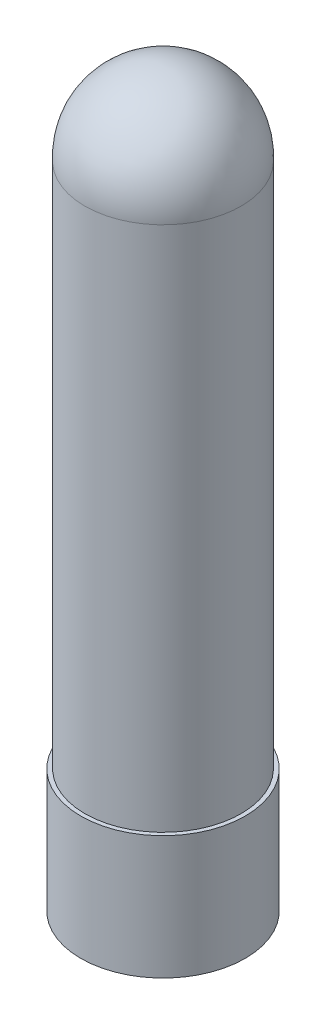
SolidWorks part; units mm, degrees
ref_plane "Front Plane" through (0, 0, 0) normal (0, 0, 1) x (1, 0, 0)
ref_plane "Top Plane" through (0, 0, 0) normal (0, 1, 0) x (1, 0, 0)
ref_plane "Right Plane" through (0, 0, 0) normal (1, 0, 0) x (0, 0, -1)
sketch "Sketch1" plane through (0, 0, 0) normal (0, 1, 0) x (1, 0, 0)
  circle A0 centre (0, 0) radius 10
extrude "Boss-Extrude1" add sketch "Sketch1" along normal blind 15
sketch "Sketch3" plane through (0, 0, 0) normal (0, -1, 0) x (1, 0, 0)
  circle A0 centre (0, 0) radius 9.5
extrude "Boss-Extrude3" add sketch "Sketch3" against normal blind 64 from surface starting at face at (0, 15, 10)
sketch "Sketch2" plane through (0, 0, 0) normal (0, 0, 1) x (1, 0, 0)
  line L0 (0, 75.9639) -> (-2.5, 62.1786)
  line L1 (-2.5, 62.1786) -> (2.5, 62.1786)
  line L2 (2.5, 62.1786) -> (0, 75.9639)
  dimension "D1" = 5
  dimension "D2" = 2.5
  dimension "D3" = 2.5
extrude "Boss-Extrude2" [suppressed] add sketch "Sketch2"
dome "Dome1" faces to dome 1 distance 10 reverse direction no elliptical dome no face at (0, 79, 9.5) parameters "D1"=10
